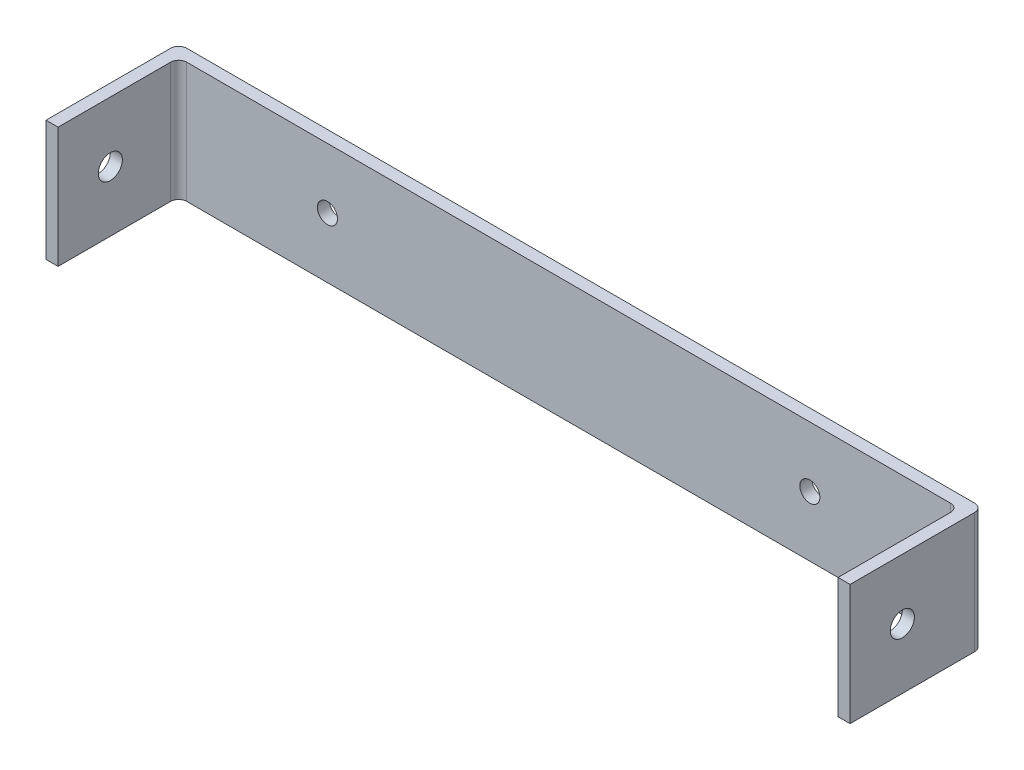
SolidWorks part; units mm, degrees
ref_plane "Plan de face" through (0, 0, 0) normal (0, 0, 1) x (1, 0, 0)
ref_plane "Plan de dessus" through (0, 0, 0) normal (0, 1, 0) x (1, 0, 0)
ref_plane "Plan de droite" through (0, 0, 0) normal (1, 0, 0) x (0, 0, -1)
sketch "Esquisse1" plane through (0, 0, 0) normal (0, 0, 1) x (1, 0, 0)
  line L1 (0, 0) -> (200, 0)
  line L2 (0, 0) -> (0, -30)
  line L3 (0, -30) -> (200, -30)
  line L4 (200, 0) -> (200, -30)
  circle A0 centre (40, -15) radius 2.5
  circle A1 centre (160, -15) radius 2.5
  dimension "D2" = 5
  dimension "D3" = 5
  dimension "D1" = 30
  dimension "D4" = 15
  dimension "D5" = 15
  dimension "D6" = 120
  dimension "D7" = 200
  dimension "D8" = 40
extrude "Boss.-Extru.1" add sketch "Esquisse1" along normal blind 3
sketch "Esquisse2" plane through (0, 0, 3) normal (0, 0, 1) x (1, 0, 0)
  line L0 (200, 0) -> (0, 0) construction
  line L1 (0, -30) -> (3, -30)
  line L2 (0, -30) -> (0, 0)
  line L3 (0, 0) -> (3, 0)
  line L4 (3, -30) -> (3, 0)
  line L5 (0, -30) -> (200, -30) construction
  line L6 (200, 0) -> (197, 0)
  line L7 (200, 0) -> (200, -30)
  line L8 (200, -30) -> (197, -30)
  line L9 (197, 0) -> (197, -30)
  point P14 (200, -15)
  dimension "D1" = 3
  dimension "D2" = 3
extrude "Boss.-Extru.2" add sketch "Esquisse2" along normal blind 30
sketch "Esquisse3" plane through (0, 0, 0) normal (-1, 0, 0) x (0, 0, 1)
  line L0 (33, 0) -> (0, 0) construction
  line L2 (0, 0) -> (0, -30) construction
  circle A0 centre (20, -15) radius 3
  point P6 (0, -17.8049)
  point P7 (-12.3046, 75.9062)
  dimension "D1" = 6
  dimension "D2" = 15
  dimension "D3" = 20
extrude "Enlèv. mat.-Extru.1" cut sketch "Esquisse3" against normal blind 229
fillet "Congé1" radius 2 4 edges at (200, -15, 0) (197, -15, 3) (0, -15, 0) (3, -15, 3)
